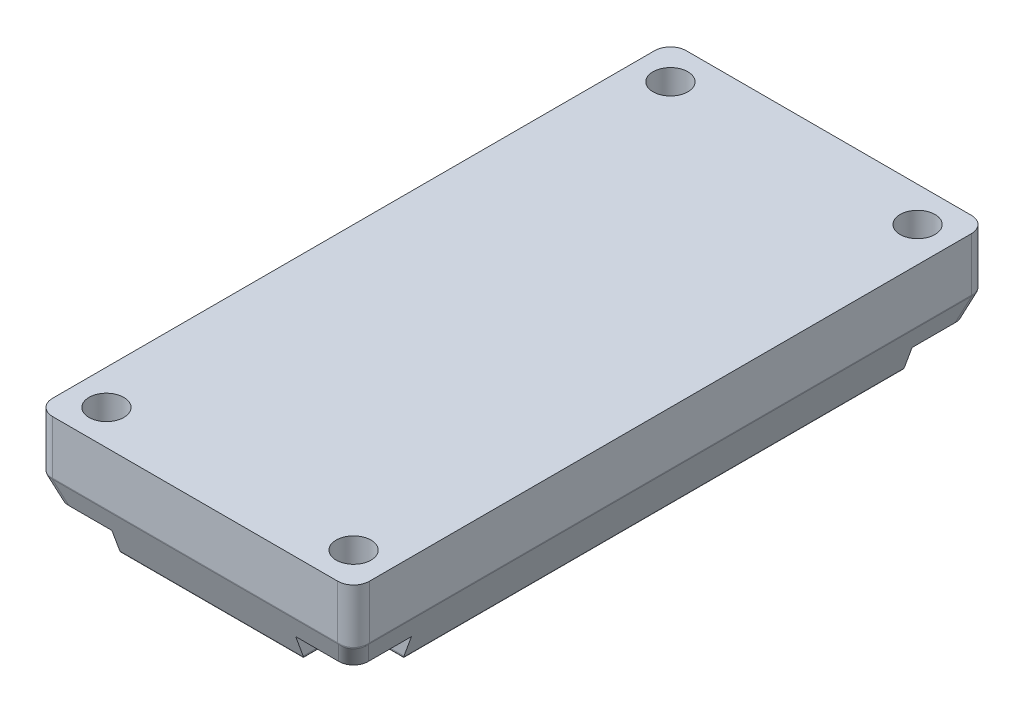
SolidWorks part; units mm, degrees
material "PC High Viscosity"
ref_plane "Front Plane" through (0, 0, 0) normal (0, 0, 1) x (1, 0, 0)
ref_plane "Top Plane" through (0, 0, 0) normal (0, 1, 0) x (1, 0, 0)
ref_plane "Right Plane" through (0, 0, 0) normal (1, 0, 0) x (0, 0, -1)
sketch "BaseS" plane through (0, 0, 0) normal (0, 1, 0) x (1, 0, 0)
  line L0 (-10, 20) -> (10, 20)
  line L1 (-10, 20) -> (-10, -20)
  line L2 (-10, -20) -> (10, -20)
  line L3 (10, 20) -> (10, -20)
  line L4 (-10, 20) -> (10, -20) construction
  line L5 (-10, -20) -> (10, 20) construction
  point P0 (0, 0)
  dimension "D1" = 20
  dimension "D2" = 40
extrude "BASE" add sketch "BaseS" along normal blind 6.4
sketch "HoleSideCutsS" plane through (0, 0, 0) normal (0, -1, 0) x (1, 0, 0)
  line L0 (-5.8, 17.6) -> (-5.8, 20)
  line L1 (-7.6, 15.8) -> (-10, 15.8)
  line L2 (-5.8, 20) -> (-10, 20)
  line L3 (-10, 20) -> (-10, 15.8)
  line L4 (-10, 20) -> (10, 20) construction
  line L5 (-10, -20) -> (-10, 20) construction
  arc A0 (-7.6, 15.8) -> (-5.8, 17.6) centre (-7.6, 17.6) ccw
  dimension "D3" = 3.6
  dimension "D1" = 4.2
extrude "HOLE SIDE CUTS" cut sketch "HoleSideCutsS" against normal blind 1.5
hole_wizard "M2 Clearance Hole1" positions "Sketch3" profile "Sketch4" hole size "M2" standard "ANSI Metric" end condition through all
sketch "Sketch3" plane through (0, 1.5, 0) normal (0, -1, 0) x (-1, 0, 0)
  line L0 (10, -20) -> (10, -15.8) construction
  line L1 (5.8, -20) -> (10, -20) construction
  point P0 (7.8, -17.8)
  dimension "D1" = 2.2
  dimension "D2" = 2.2
sketch "Sketch4" plane through (-7.8, 1.5, 17.8) normal (1, 0, 0) x (0, 0, -1)
  line L0 (0, 0) -> (0, 4.9)
  line L1 (0, 4.9) -> (1.1, 4.9)
  line L2 (1.1, 4.9) -> (1.1, 0)
  line L5 (1.1, 0) -> (0, 0)
  line L11 (0, -6.35) -> (0, 107.95) construction
  dimension "Thru Hole Dia." = 2.2
  dimension "Thru Hole Depth" = 4.9
mirror "HOLE FEATURES HM" about plane through (0, 0, 0) normal (1, 0, 0) of "M2 Clearance Hole1", "HOLE SIDE CUTS"
mirror "HOLE FEATURE VM" about plane through (0, 0, 0) normal (0, 0, 1) of "HOLE FEATURES HM", "HOLE SIDE CUTS", "M2 Clearance Hole1"
sketch "SideChamfer1S" plane through (0, 0, 0) normal (0, 0, 1) x (1, 0, 0)
  line L0 (10, 3) -> (10, 0)
  line L1 (10, 6.4) -> (10, 1.5) construction
  line L2 (10, 0) -> (8.9081, 0)
  line L3 (10, 0) -> (7.6, 0) construction
  line L4 (8.9081, 0) -> (10, 3)
  dimension "D1" = 3
  dimension "D2" = 20
extrude "SIDE CHAMFER 1" cut sketch "SideChamfer1S" against normal through all both and the other way through all
mirror "SC1 HM" about plane through (0, 0, 0) normal (1, 0, 0) of "SIDE CHAMFER 1"
sketch "SideChamfer2S" plane through (0, 0, 0) normal (1, 0, 0) x (0, 0, -1)
  line L0 (20, 3) -> (20, 0)
  line L1 (20, 6.4) -> (20, 3) construction
  line L2 (20, 0) -> (18.9081, 0)
  line L4 (18.9081, 0) -> (20, 3)
  dimension "D1" = 3
  dimension "D2" = 20
extrude "SIDE CHAMFER 2" cut sketch "SideChamfer2S" against normal through all both and the other way through all
mirror "SC2 VM" about plane through (0, 0, 0) normal (0, 0, 1) of "SIDE CHAMFER 2"
fillet "BASE F" radius 1 8 edges at (-9.727, 2.25, -19.727) (-10, 4.7, -20) (9.727, 2.25, -19.727) (10, 4.7, -20) (-9.727, 2.25, 19.727) (-10, 4.7, 20) (9.727, 2.25, 19.727) (10, 4.7, 20)
fillet "BASE BOTTOM F" radius 0.2 32 edges at (9.9996, 2.9988, -19.0293) (9.7071, 2.9341, -19.7071) (9.0293, 2.9988, -19.9996) (0, 3, -20) (-9.0293, 2.9988, -19.9996) (-9.7071, 2.9341, -19.7071) (-9.9996, 2.9988, -19.0293) (-10, 3, 0) (-9.9996, 2.9988, 19.0293) (-9.7071, 2.9341, 19.7071) (-9.0293, 2.9988, 19.9996) (0, 3, 20) (9.0293, 2.9988, 19.9996) (9.7071, 2.9341, 19.7071) (9.9996, 2.9988, 19.0293) (5.8, 0, 18.254) (6.3272, 0, 16.3272) (8.254, 0, 15.8) (8.9081, 0, 0) (8.254, 0, -15.8) (6.3272, 0, -16.3272) (5.8, 0, -18.254) (0, 0, -18.9081) (-5.8, 0, -18.254) (-6.3272, 0, -16.3272) (-8.254, 0, -15.8) (-8.9081, 0, 0) (-8.254, 0, 15.8) (-6.3272, 0, 16.3272) (-5.8, 0, 18.254) (0, 0, 18.9081) (10, 3, 0)
